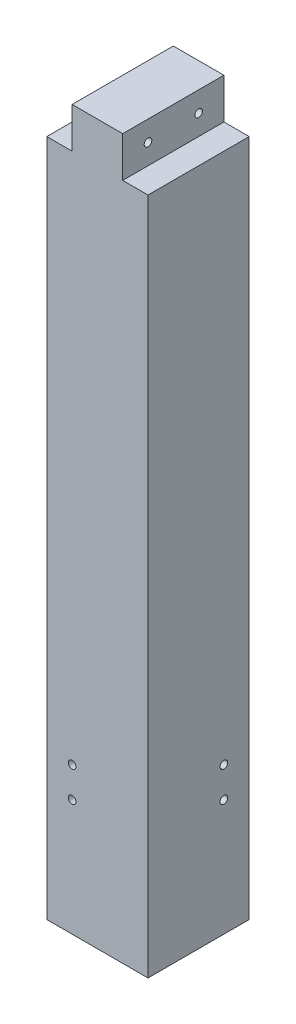
SolidWorks part; units mm, degrees
material "Pine"
ref_plane "Front Plane" through (0, 0, 0) normal (0, 0, 1) x (1, 0, 0)
ref_plane "Top Plane" through (0, 0, 0) normal (0, 1, 0) x (1, 0, 0)
ref_plane "Right Plane" through (0, 0, 0) normal (1, 0, 0) x (0, 0, -1)
sketch "Sketch1" plane through (0, 0, 0) normal (0, 0, 1) x (1, 0, 0)
  line L1 (63.5, 425.45) -> (-63.5, 425.45)
  line L2 (63.5, 425.45) -> (63.5, -425.45)
  line L3 (63.5, -425.45) -> (-63.5, -425.45)
  line L4 (-63.5, 425.45) -> (-63.5, -425.45)
  line L5 (63.5, 425.45) -> (-63.5, -425.45) construction
  line L6 (63.5, -425.45) -> (-63.5, 425.45) construction
  line L7 (31.75, 476.25) -> (-31.75, 476.25)
  line L8 (31.75, 476.25) -> (31.75, 374.65)
  line L9 (31.75, 374.65) -> (-31.75, 374.65)
  line L10 (-31.75, 476.25) -> (-31.75, 374.65)
  line L11 (31.75, 476.25) -> (-31.75, 374.65) construction
  line L12 (31.75, 374.65) -> (-31.75, 476.25) construction
  line L13 (0, -222.25) -> (-31.75, -222.25)
  line L14 (0, -222.25) -> (0, -298.45)
  line L15 (0, -298.45) -> (-31.75, -298.45)
  line L16 (-31.75, -222.25) -> (-31.75, -298.45)
  line L17 (0, -222.25) -> (-31.75, -298.45) construction
  line L18 (0, -298.45) -> (-31.75, -222.25) construction
  point P0 (0, 0)
  point P6 (0, 425.45)
  point P11 (-15.875, -260.35)
  dimension "D1" = 850.9
  dimension "D2" = 127
  dimension "D3" = 101.6
  dimension "D4" = 63.5
  dimension "D5" = 31.75
  dimension "D6" = 127
  dimension "D7" = 76.2
  dimension "D8" = 31.75
extrude "Boss-Extrude1" add sketch "Sketch1" against normal blind 127 contours L7 L10 L1 L8 | L3 L4 L1 L2 region at (0, 450.85, 0)
sketch "Sketch4" plane through (-63.5, 0, 0) normal (-1, 0, 0) x (0, 0, 1)
  line L1 (-31.75, -222.25) -> (-63.5, -222.25)
  line L2 (-31.75, -222.25) -> (-31.75, -298.45)
  line L3 (-31.75, -298.45) -> (-63.5, -298.45)
  line L4 (-63.5, -222.25) -> (-63.5, -298.45)
  line L5 (-31.75, -222.25) -> (-63.5, -298.45) construction
  line L6 (-31.75, -298.45) -> (-63.5, -222.25) construction
  line L7 (-127, -425.45) -> (0, -425.45) construction
  line L8 (0, 425.45) -> (0, -425.45) construction
  point P0 (-47.625, -260.35)
  dimension "D1" = 76.2
  dimension "D2" = 31.75
  dimension "D3" = 31.75
  dimension "D4" = 127
extrude "Cut-Extrude3" cut sketch "Sketch4" against normal blind 63.5
sketch "Sketch5" plane through (0, 0, -127) normal (0, 0, -1) x (-1, 0, 0)
  line L1 (0, -222.25) -> (-31.75, -222.25)
  line L2 (0, -222.25) -> (0, -298.45)
  line L3 (0, -298.45) -> (-31.75, -298.45)
  line L4 (-31.75, -222.25) -> (-31.75, -298.45)
  line L5 (0, -222.25) -> (-31.75, -298.45) construction
  line L6 (0, -298.45) -> (-31.75, -222.25) construction
  line L7 (-63.5, -425.45) -> (63.5, -425.45) construction
  line L8 (-63.5, 425.45) -> (-63.5, -425.45) construction
  point P0 (-15.875, -260.35)
  dimension "D1" = 76.2
  dimension "D2" = 31.75
  dimension "D3" = 31.75
  dimension "D4" = 127
extrude "Cut-Extrude4" cut sketch "Sketch5" against normal blind 63.246
sketch "Sketch7" plane through (63.5, 0, 0) normal (1, 0, 0) x (0, 0, -1)
  line L0 (95.25, -222.25) -> (95.25, -298.45) construction
  line L4 (127, -298.45) -> (127, -222.25)
  line L5 (63.754, -298.45) -> (127, -298.45)
  line L6 (63.754, -222.25) -> (63.754, -298.45)
  line L7 (127, -222.25) -> (63.754, -222.25)
  line L8 (127, -298.45) -> (127, -222.25)
  line L9 (63.754, -298.45) -> (127, -298.45)
  line L10 (63.754, -222.25) -> (63.754, -298.45)
  line L11 (127, -222.25) -> (63.754, -222.25)
  circle A0 centre (95.25, -279.4) radius 4.7625
  circle A1 centre (95.25, -241.3) radius 4.7625
  point P10 (95.25, -260.35)
  dimension "D2" = 9.525
  dimension "D3" = 19.05
  dimension "D4" = 19.05
  dimension "D5" = 31.75
  dimension "D1" = 0
extrude "Cut-Extrude6" cut sketch "Sketch7" against normal blind 69.85 contours A0 L0 | L0 A0 | A1 L0 | L0 A1 region at (63.5, -241.3, -97.2713) region at (63.5, -241.3, -93.2287) region at (63.5, -279.4, -97.2713) region at (63.5, -279.4, -93.2287)
sketch "Sketch8" plane through (0, 0, 0) normal (0, 0, 1) x (1, 0, 0)
  line L0 (-31.75, -222.25) -> (-31.75, -298.45) construction
  line L4 (-63.5, -222.25) -> (-63.5, -298.45)
  line L5 (0, -222.25) -> (-63.5, -222.25)
  line L6 (0, -298.45) -> (0, -222.25)
  line L7 (-63.5, -298.45) -> (0, -298.45)
  line L8 (-63.5, -222.25) -> (-63.5, -298.45)
  line L9 (0, -222.25) -> (-63.5, -222.25)
  line L10 (0, -298.45) -> (0, -222.25)
  line L11 (-63.5, -298.45) -> (0, -298.45)
  circle A0 centre (-31.75, -279.4) radius 4.7625
  circle A1 centre (-31.75, -241.3) radius 4.7625
  point P10 (-31.75, -260.35)
  dimension "D2" = 9.525
  dimension "D3" = 19.05
  dimension "D4" = 19.05
  dimension "D5" = 31.75
  dimension "D1" = 0
extrude "Cut-Extrude8" cut sketch "Sketch8" against normal blind 69.85 contours A0 L0 | L0 A0 | L0 A1 | A1 L0 region at (-29.7287, -241.3, 0) region at (-33.7713, -241.3, 0) region at (-29.7287, -279.4, 0) region at (-33.7713, -279.4, 0)
sketch "Sketch9" plane through (-31.75, 0, 0) normal (-1, 0, 0) x (0, 0, 1)
  line L0 (-127, 450.85) -> (0, 450.85) construction
  line L1 (-127, 476.25) -> (-127, 425.45) construction
  line L2 (0, 476.25) -> (0, 425.45) construction
  circle A0 centre (-95.25, 450.85) radius 4.7625
  circle A1 centre (-31.75, 450.85) radius 4.7625
  point P10 (-63.5, 450.85)
  dimension "D1" = 9.525
  dimension "D2" = 31.75
  dimension "D3" = 31.75
extrude "Cut-Extrude9" cut sketch "Sketch9" against normal through all
sketch "Sketch6" plane through (0, 0, 0) normal (0, 0, 1) x (1, 0, 0)
  line L0 (-31.75, -222.25) -> (-31.75, -298.45) construction
  line L4 (-63.5, -222.25) -> (-63.5, -298.45)
  line L5 (0, -222.25) -> (-63.5, -222.25)
  line L6 (0, -298.45) -> (0, -222.25)
  line L7 (-63.5, -298.45) -> (0, -298.45)
  line L8 (-63.5, -222.25) -> (-63.5, -298.45)
  line L9 (0, -222.25) -> (-63.5, -222.25)
  line L10 (0, -298.45) -> (0, -222.25)
  line L11 (-63.5, -298.45) -> (0, -298.45)
  circle A0 centre (-31.75, -241.3) radius 4.7625
  circle A1 centre (-31.75, -279.4) radius 4.7625
  point P10 (-31.75, -260.35)
  dimension "D2" = 9.525
  dimension "D3" = 19.05
  dimension "D4" = 19.05
  dimension "D1" = 0
